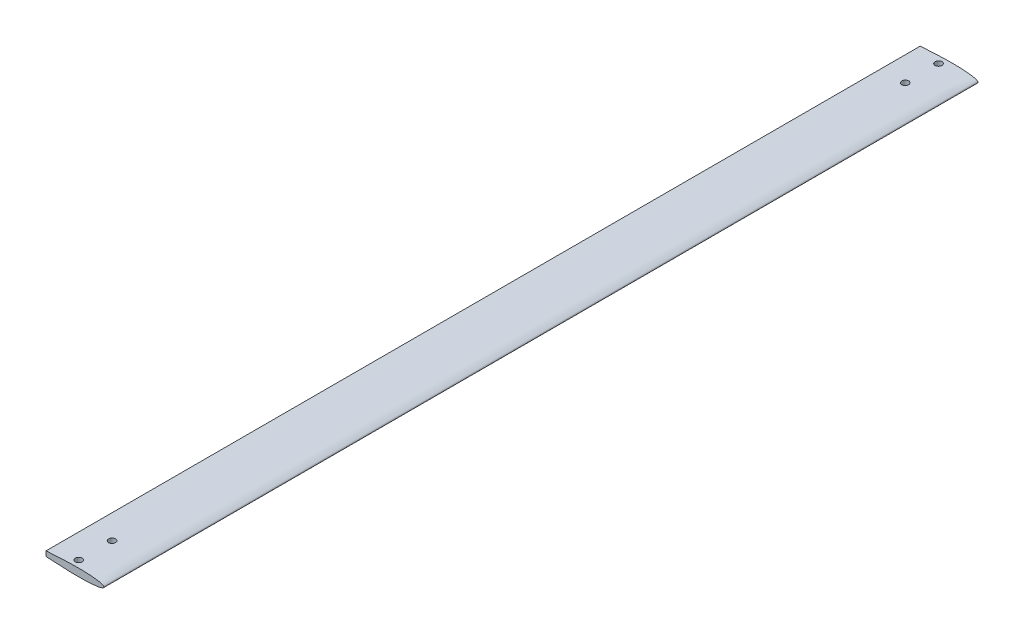
SolidWorks part; units mm, degrees
ref_plane "Front Plane" through (0, 0, 0) normal (0, 0, 1) x (1, 0, 0)
ref_plane "Top Plane" through (0, 0, 0) normal (0, 1, 0) x (1, 0, 0)
ref_plane "Right Plane" through (0, 0, 0) normal (1, 0, 0) x (0, 0, -1)
sketch "Sketch1" plane through (0, 0, 0) normal (0, 0, 1) x (1, 0, 0)
  line L0 (-60.7097, 2.5789) -> (-60.7097, -2.5789)
  spline S0 degree 3 poles (-60.7097, 2.5789) (-59.9511, 2.6331) (-57.6888, 2.7949) (-53.8875, 3.0398) (-49.2895, 3.3117) (-44.6404, 3.5514) (-39.9913, 3.7517) (-35.3931, 3.9034) (-30.896, 3.9986) (-26.5493, 4.0302) (-22.4005, 3.9926) (-18.4952, 3.8824) (-14.8759, 3.6986) (-11.5822, 3.4427) (-8.6499, 3.1186) (-6.11, 2.7333) (-3.9903, 2.2928) (-2.3063, 1.8123) (-1.076, 1.2846) (-0.2563, 0.7395) (0.106, 0) (-0.2563, -0.7395) (-1.076, -1.2846) (-2.3063, -1.8123) (-3.9903, -2.2928) (-6.11, -2.7333) (-8.6499, -3.1186) (-11.5822, -3.4427) (-14.8759, -3.6986) (-18.4952, -3.8824) (-22.4005, -3.9926) (-26.5493, -4.0302) (-30.896, -3.9986) (-35.3931, -3.9034) (-39.9913, -3.7517) (-44.6404, -3.5514) (-49.2895, -3.3117) (-53.8875, -3.0398) (-57.6888, -2.7949) (-59.9511, -2.6331) (-60.7097, -2.5789) knots 0 0 0 0 0.018499 0.055171 0.092655 0.130539 0.168407 0.205846 0.242449 0.277819 0.311577 0.343364 0.372846 0.399719 0.423712 0.444594 0.46218 0.476354 0.487106 0.494669 0.5 0.505331 0.512894 0.523646 0.53782 0.555406 0.576288 0.600281 0.627154 0.656636 0.688423 0.722181 0.757551 0.794154 0.831593 0.869461 0.907345 0.944829 0.981501 1 1 1 1
extrude "Boss-Extrude1" add sketch "Sketch1" along normal mid plane 917.4
ref_plane "Plane1" through (0, -10, 0) normal (0, 1, 0) x (1, 0, 0)
sketch "Sketch2" plane through (0, -10, 0) normal (0, 1, 0) x (1, 0, 0)
  circle A0 centre (-33.9, -451.2) radius 3.6
  circle A1 centre (-33.9, -416.2) radius 3.6
  circle A2 centre (-33.9, 416.2) radius 3.6
  circle A3 centre (-33.9, 451.2) radius 3.6
extrude "Cut-Extrude1" cut sketch "Sketch2" along normal blind 20
